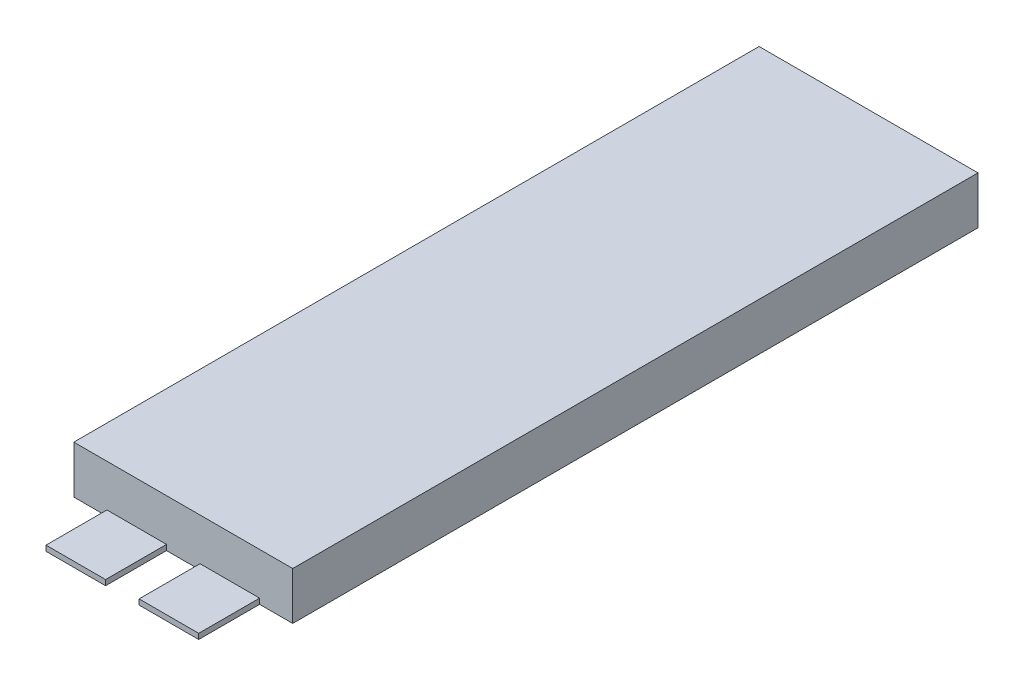
SolidWorks part; units mm, degrees
ref_plane "Front Plane" through (0, 0, 0) normal (0, 0, 1) x (1, 0, 0)
ref_plane "Top Plane" through (0, 0, 0) normal (0, 1, 0) x (1, 0, 0)
ref_plane "Right Plane" through (0, 0, 0) normal (1, 0, 0) x (0, 0, -1)
sketch "Sketch1" plane through (0, 0, 0) normal (0, 1, 0) x (1, 0, 0)
  line L2 (-23, 72) -> (23, 72)
  line L5 (-19, 72) -> (-19, 90)
  line L6 (-19, 90) -> (-4, 90)
  line L7 (-4, 90) -> (-4, 72)
  line L8 (4, 72) -> (4, 90)
  line L9 (4, 90) -> (19, 90)
  line L10 (19, 90) -> (19, 72)
  line L11 (0, 72) -> (0, 180.6197) construction
  line L13 (23, -72) -> (-23, -72)
  line L14 (23, -72) -> (23, 72)
  line L16 (-23, -72) -> (-23, 72)
  line L17 (23, -72) -> (-23, 72) construction
  line L18 (23, 72) -> (-23, -72) construction
  point P0 (0, 0)
  point P16 (-11.5, 90)
  point P17 (11.5, 90)
  dimension "D1" = 144
  dimension "D2" = 46
  dimension "D3" = 15
  dimension "D4" = 23
  dimension "D5" = 18
extrude "cell" add sketch "Sketch1" along normal blind 10 contours L2 L14 L13 L16
sketch "Sketch2" plane through (0, 0, 72) normal (0, 0, 1) x (1, 0, 0)
  line L0 (23, 0) -> (-23, 0) construction
  line L1 (-16.0434, 0) -> (-3.5183, 0)
  line L2 (-16.0434, 0) -> (-16.0434, 1.1329)
  line L3 (-16.0434, 1.1329) -> (-3.5183, 1.1329)
  line L4 (-3.5183, 0) -> (-3.5183, 1.1329)
  line L5 (0, 0) -> (0, 10) construction
  line L6 (23, 10) -> (-23, 10) construction
  line L7 (3.5183, 0) -> (3.5183, 1.1329)
  line L8 (16.0434, 1.1329) -> (3.5183, 1.1329)
  line L9 (16.0434, 0) -> (16.0434, 1.1329)
  line L10 (16.0434, 0) -> (3.5183, 0)
extrude "Boss-Extrude1" add sketch "Sketch2" along normal blind 12.8
equation "\"D1@cell\" = 10.00mm"
